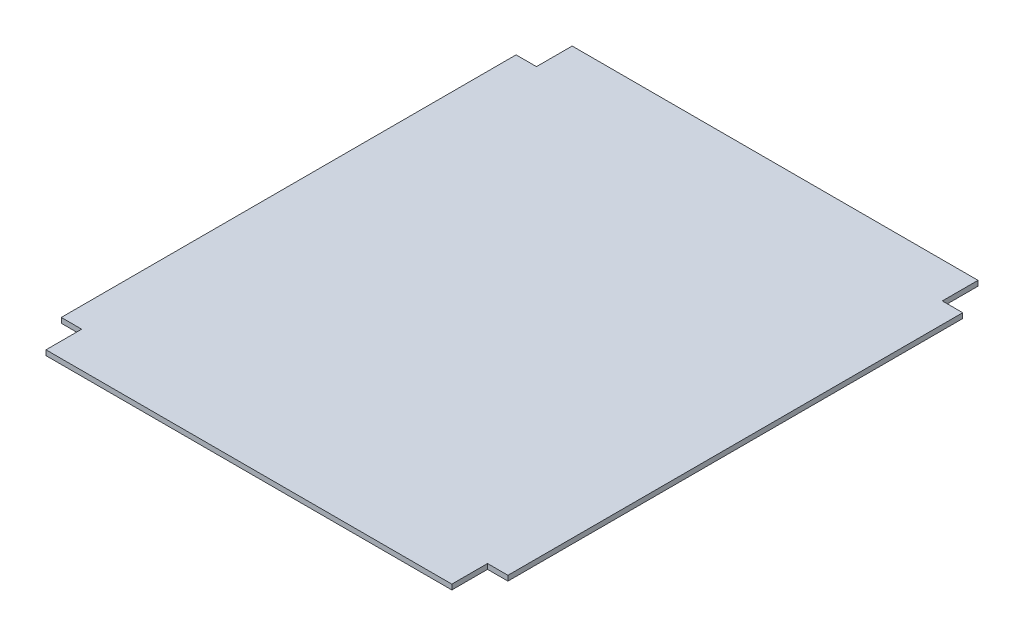
SolidWorks part; units mm, degrees
ref_plane "Front Plane" through (0, 0, 0) normal (0, 0, 1) x (1, 0, 0)
ref_plane "Top Plane" through (0, 0, 0) normal (0, 1, 0) x (1, 0, 0)
ref_plane "Right Plane" through (0, 0, 0) normal (1, 0, 0) x (0, 0, -1)
sketch "Sketch1" plane through (0, 0, 0) normal (0, 1, 0) x (1, 0, 0)
  line L0 (0, 0) -> (0, 3.5)
  line L1 (0, 3.5) -> (-2, 3.5)
  line L2 (-2, 3.5) -> (-2, 48.1)
  line L3 (-2, 48.1) -> (0, 48.1)
  line L4 (0, 48.1) -> (0, 51.6)
  line L5 (0, 51.6) -> (39.8, 51.6)
  line L6 (39.8, 51.6) -> (39.8, 48.1)
  line L7 (39.8, 48.1) -> (41.8, 48.1)
  line L8 (41.8, 48.1) -> (41.8, 3.5)
  line L9 (41.8, 3.5) -> (39.8, 3.5)
  line L10 (39.8, 3.5) -> (39.8, 0)
  line L11 (39.8, 0) -> (0, 0)
  dimension "D1" = 44.6
  dimension "D2" = 51.6
  dimension "D3" = 39.8
  dimension "D4" = 2
extrude "Boss-Extrude1" add sketch "Sketch1" along normal blind 0.5
